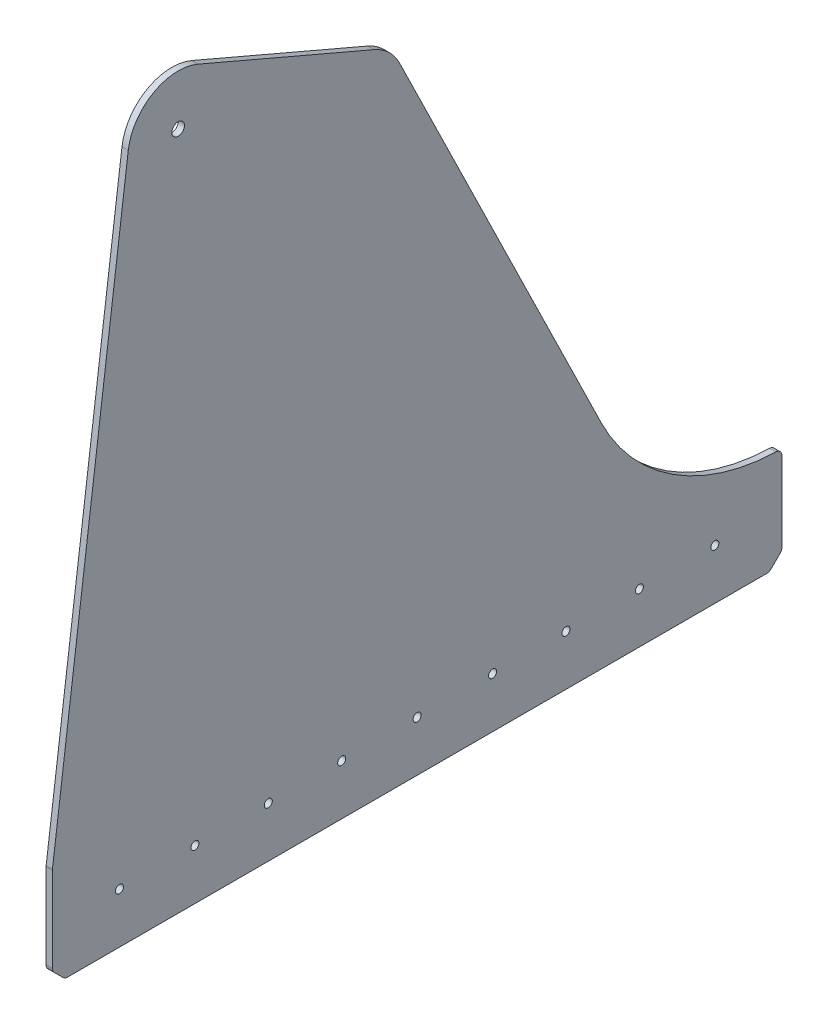
SolidWorks part; units mm, degrees
ref_plane "Front Plane" through (0, 0, 0) normal (0, 0, 1) x (1, 0, 0)
ref_plane "Top Plane" through (0, 0, 0) normal (0, 1, 0) x (1, 0, 0)
ref_plane "Right Plane" through (0, 0, 0) normal (1, 0, 0) x (0, 0, -1)
sketch "Sketch2" plane through (0, 0, 0) normal (1, 0, 0) x (0, 0, -1)
  line L0 (0, 0) -> (0, 50.8)
  line L1 (0, 50.8) -> (38.311, 346.1672)
  line L4 (368.3, 50.8) -> (368.3, 0)
  line L5 (368.3, 0) -> (0, 0)
  line L6 (73.5056, 366.2463) -> (162.4056, 328.1463)
  line L7 (175.2177, 315.9585) -> (277.0291, 107.7662)
  line L8 (368.3, 50.8) -> (419.4553, 50.8) construction
  line L9 (0, 374.65) -> (368.3, 374.65) construction
  arc A0 (38.311, 346.1672) -> (73.5056, 366.2463) centre (63.5, 342.9) cw
  arc A1 (162.4056, 328.1463) -> (175.2177, 315.9585) centre (152.4, 304.8) cw
  arc A2 (277.0291, 107.7662) -> (368.3, 50.8) centre (368.3, 152.4) ccw
  point P13 (0, 374.65)
  point P15 (368.3, 374.65)
  point P16 (170.1907, 302.4135)
  dimension "D6" = 25.4
  dimension "D3" = 101.6
  dimension "D7" = 25.4
  dimension "D1" = 368.3
  dimension "D2" = 50.8
  dimension "D4" = 304.8
  dimension "D5" = 342.9
  dimension "D8" = 374.65
  dimension "D9" = 304.8
  dimension "D10" = 152.4
extrude "Plate" add sketch "Sketch2" along normal blind 3.175
sketch "Sketch4" plane through (3.175, 0, 0) normal (1, 0, 0) x (0, 0, -1)
  line L4 (184.15, 25.4) -> (222.25, 25.4) construction
  line L7 (222.25, 25.4) -> (259.2917, 25.4) construction
  line L8 (259.2917, 25.4) -> (296.3333, 25.4) construction
  line L9 (296.3333, 25.4) -> (334.4333, 25.4) construction
  line L12 (184.15, 25.4) -> (146.05, 25.4) construction
  line L13 (146.05, 25.4) -> (109.0083, 25.4) construction
  line L14 (109.0083, 25.4) -> (71.9667, 25.4) construction
  line L15 (71.9667, 25.4) -> (33.8667, 25.4) construction
  line L18 (0, 0) -> (368.3, 0) construction
  line L19 (368.3, 0) -> (368.3, 50.8) construction
  point P0 (184.15, 25.4)
  point P10 (222.25, 25.4)
  point P12 (259.2917, 25.4)
  point P14 (296.3333, 25.4)
  point P16 (334.4333, 25.4)
  point P18 (146.05, 25.4)
  point P20 (109.0083, 25.4)
  point P22 (71.9667, 25.4)
  point P24 (33.8667, 25.4)
  point P50 (184.15, 0)
  point P51 (0, 0)
  point P54 (368.3, 25.4)
  dimension "Small-Large Gear Spacing" = 38.1
  dimension "Small to Small Hole Spacing" = 37.0417
  dimension "D1" = 300.5667
hole_wizard "Drive Holes" positions "Sketch4" profile "Sketch6" hole size "#8" standard "ANSI Inch" end condition through all
sketch "Sketch6" plane through (3.175, 25.4, -184.15) normal (0, 1, 0) x (0, 0, -1)
  line L0 (0, 0) -> (0, 3.175)
  line L1 (0, 3.175) -> (2.032, 3.175)
  line L2 (2.032, 3.175) -> (2.032, 0)
  line L5 (2.032, 0) -> (0, 0)
  line L11 (0, -6.35) -> (0, 107.95) construction
  dimension "Thru Hole Dia." = 4.064
  dimension "Thru Hole Depth" = 3.175
sketch "Sketch3" plane through (3.175, 0, 0) normal (1, 0, 0) x (0, 0, -1)
  circle A0 centre (63.5, 342.9) radius 3.175
  dimension "D1" = 6.35
extrude "Tube Pivot Holes" cut sketch "Sketch3" against normal through all
chamfer "Bottom Corner Chamfer" distance 6.35 angle 45 2 edges at (1.5875, 0, -368.3) (1.5875, 0, 0)
fillet "Bottom Corner Fillet" radius 3.175 6 edges at (1.5875, 50.8, 0) (1.5875, 0, -6.35) (1.5875, 6.35, 0) (1.5875, 0, -361.95) (1.5875, 6.35, -368.3) (1.5875, 50.8, -368.3)
equation "\"Small to Small Gear Spacing\"= ( 35 / 24 )"
equation "\"Small to Big Gear Spacing\" = ( 35 / 48 ) + ( 37 / 48 )"
equation "\"Small-Large Gear Spacing@Sketch4\"= \"Small to Big Gear Spacing\""
equation "\"Small to Small Hole Spacing@Sketch4\"= \"Small to Small Gear Spacing\""
